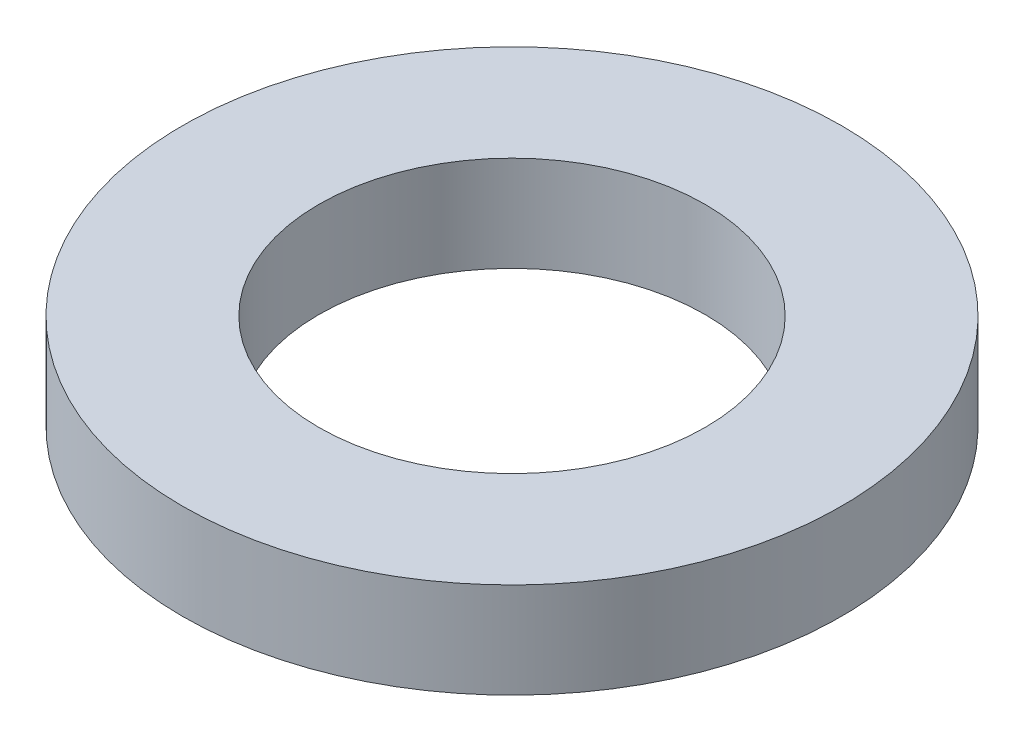
SolidWorks part; units mm, degrees
ref_plane "Front Plane" through (0, 0, 0) normal (0, 0, 1) x (1, 0, 0)
ref_plane "Top Plane" through (0, 0, 0) normal (0, 1, 0) x (1, 0, 0)
ref_plane "Right Plane" through (0, 0, 0) normal (1, 0, 0) x (0, 0, -1)
sketch "Sketch1" plane through (0, 0, 0) normal (0, 1, 0) x (1, 0, 0)
  circle A0 centre (0, 0) radius 72.5
  dimension "FLANGE_OD" = 145
extrude "Boss-Extrude1" add sketch "Sketch1" along normal blind 21
sketch "Sketch2" plane through (0, 0, 0) normal (0, 1, 0) x (1, 0, 0)
  circle A0 centre (0, 0) radius 42.5
  dimension "BORE_D" = 85
extrude "Cut-Extrude1" cut sketch "Sketch2" along normal through all
sketch "Sketch3" plane through (0, 21, 0) normal (0, 1, 0) x (1, 0, 0)
  circle A0 centre (0, 0) radius 23.9852 construction
  circle A1 centre (-23.9852, 0) radius 3.2881
  dimension "BOLT_D" = 6.5762
  dimension "BOLT_PCD" = 47.9704
extrude "Cut-Extrude2" cut sketch "Sketch3" against normal blind 17.3067 rebuild error yes
pattern_circular "CirPattern1" count 6 over 360 rebuild error yes
